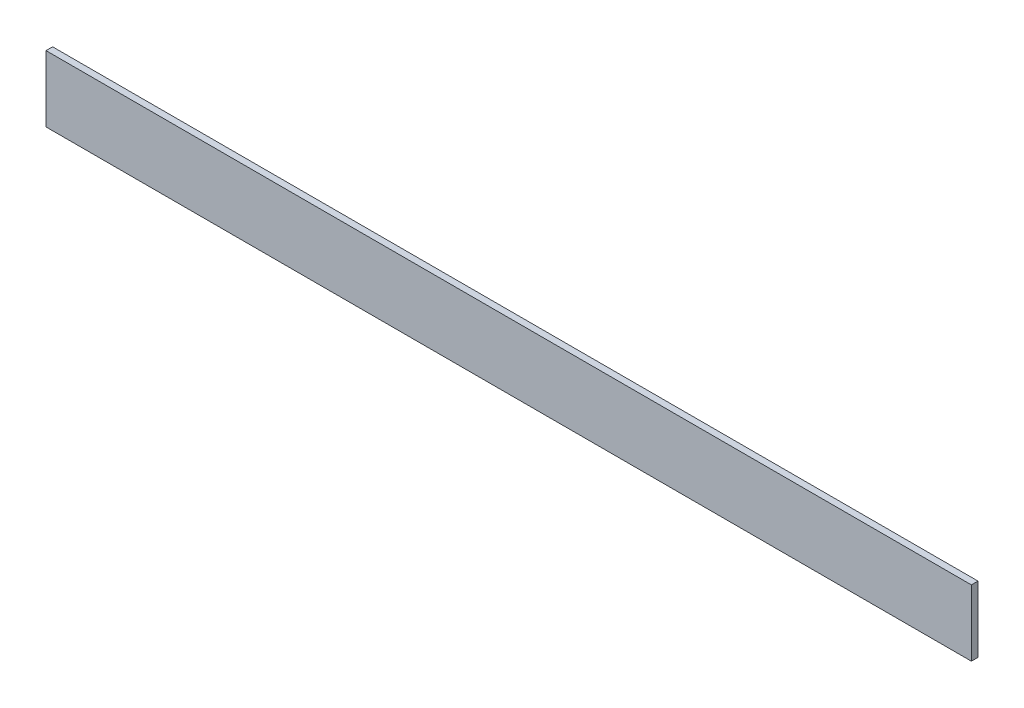
SolidWorks part; units mm, degrees
ref_plane "Ön Düzlem" through (0, 0, 0) normal (0, 0, 1) x (1, 0, 0)
ref_plane "Üst Düzlem" through (0, 0, 0) normal (0, 1, 0) x (1, 0, 0)
ref_plane "Sağ Düzlem" through (0, 0, 0) normal (1, 0, 0) x (0, 0, -1)
sketch "Çizim1" plane through (0, 0, 0) normal (0, 0, 1) x (1, 0, 0)
  line L1 (0, 0) -> (1400, 0)
  line L2 (0, 0) -> (0, -100)
  line L3 (0, -100) -> (1400, -100)
  line L4 (1400, 0) -> (1400, -100)
  dimension "D1" = 1400
  dimension "D2" = 100
base flange "Taban-Flanş1" sketch "Çizim1" thickness 10 reverse thickness direction no parameters "D1"=5
sketch "Büküm-Çizgileri1" [suppressed] plane through (0, 0, 0) normal (0, 1, 0) x (1, 0, 0)
sketch "Sınırlandırma-Kutusu1" [suppressed] plane through (0, 0, 0) normal (0, 1, 0) x (1, 0, 0)
sheet metal parameters "Sac-Levha1" thickness 10 parameters "D1"=5
flat pattern "Düz-Çoğaltma1" [suppressed]
sketch "Büküm-Çizgileri2" plane through (0, 0, 0) normal (0, 1, 0) x (1, 0, 0)
sketch3d "Sınırlandırma-Kutusu2" [suppressed]
  line L0 (0, -100, 0) -> (1400, -100, 0) construction
  line L1 (0, 0, 0) -> (1400, 0, 0) construction
  line L2 (0, -100, 0) -> (0, 0, 0) construction
  line L3 (1400, -100, 0) -> (1400, 0, 0) construction
